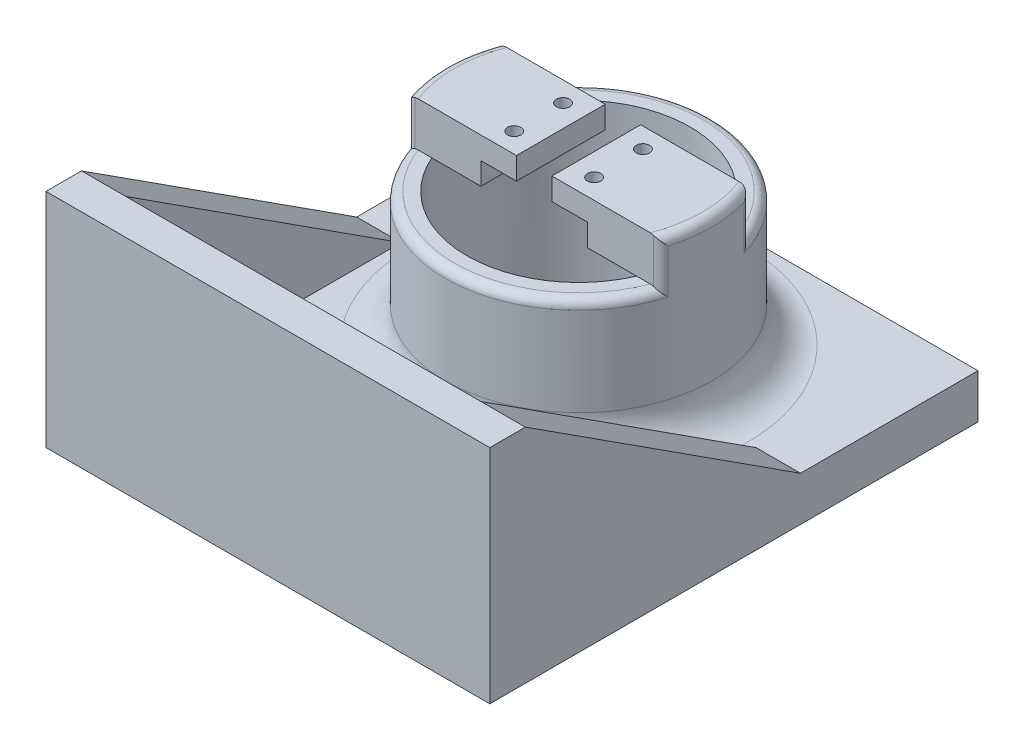
SolidWorks part; units mm, degrees
ref_plane "Front Plane" through (0, 0, 0) normal (0, 0, 1) x (1, 0, 0)
ref_plane "Top Plane" through (0, 0, 0) normal (0, 1, 0) x (1, 0, 0)
ref_plane "Right Plane" through (0, 0, 0) normal (1, 0, 0) x (0, 0, -1)
sketch "Sketch2" plane through (0, 0, 0) normal (0, 1, 0) x (1, 0, 0)
  line L0 (0, 49.9838) -> (0, -58.6525) construction
  line L2 (-50, -70) -> (50, -70)
  line L7 (-50, -70) -> (-50, 40)
  line L8 (-50, 40) -> (50, 40)
  line L9 (50, -70) -> (50, 40)
  line L10 (-50, -70) -> (50, 40) construction
  line L11 (-50, 40) -> (50, -70) construction
  point P3 (0, -15)
  dimension "D1" = 100
  dimension "D2" = 110
  dimension "D3" = 15
extrude "Boss-Extrude1" add sketch "Sketch2" along normal blind 10
sketch "Sketch3" plane through (0, 10, 0) normal (0, 1, 0) x (1, 0, 0)
  line L0 (0, -52.9301) -> (0, 51.772) construction
  circle A1 centre (0, 0) radius 30
  dimension "D1" = 60
extrude "Boss-Extrude2" add sketch "Sketch3" along normal blind 30
sketch "Sketch6" plane through (0, 40, 0) normal (0, 1, 0) x (1, 0, 0)
  circle A0 centre (0, 0) radius 25.15
  dimension "D1" = 50.3
extrude "Cut-Extrude1" cut sketch "Sketch6" against normal through all
sketch "Sketch8" plane through (0, 10, 0) normal (0, 1, 0) x (1, 0, 0)
  line L0 (0, 0) -> (0, -70) construction
  line L1 (-50, -70) -> (50, -70) construction
  line L2 (-23.6557, -50) -> (29.1004, -50) construction
  line L3 (10.3, -31.3978) -> (10.3, -63.6631) construction
  line L9 (-10.7, -60.5) -> (31.3, -60.5)
  line L10 (-10.7, -60.5) -> (-10.7, -39.5)
  line L11 (-10.7, -39.5) -> (31.3, -39.5)
  line L12 (31.3, -60.5) -> (31.3, -39.5)
  line L13 (-10.7, -60.5) -> (31.3, -39.5) construction
  line L14 (-10.7, -39.5) -> (31.3, -60.5) construction
  circle A2 centre (35.2, -45) radius 2.25
  circle A3 centre (35.2, -55) radius 2.25
  circle A4 centre (-14.6, -55) radius 2.25
  circle A5 centre (-14.6, -45) radius 2.25
  point P7 (10.3, -50)
  dimension "D4" = 4.5
  dimension "D1" = 50
  dimension "D2" = 42
  dimension "D3" = 21
  dimension "D5" = 10
  dimension "D6" = 10.3
  dimension "D7" = 49.8
extrude "Cut-Extrude2" cut sketch "Sketch8" against normal through all
sketch "Sketch9" plane through (0, 40, 0) normal (0, 1, 0) x (1, 0, 0)
  line L0 (0, 30) -> (0, -30) construction
  line L1 (-30, 0) -> (30, 0) construction
  line L2 (-28.2843, -10) -> (-4, -10)
  line L3 (-4, -10) -> (-4, 10)
  line L4 (-28.2843, 10) -> (-4, 10)
  line L5 (28.2843, -10) -> (4, -10)
  line L6 (4, -10) -> (4, 10)
  line L7 (28.2843, 10) -> (4, 10)
  circle A0 centre (0, 0) radius 30 construction
  circle A1 centre (0, 0) radius 30 construction
  arc A2 (-28.2843, 10) -> (-28.2843, -10) centre (0, 0) ccw
  circle A3 centre (-9, -5.5) radius 1.5
  circle A4 centre (-9, 5.5) radius 1.5
  circle A5 centre (9, -5.5) radius 1.5
  circle A6 centre (9, 5.5) radius 1.5
  arc A7 (28.2843, -10) -> (28.2843, 10) centre (0, 0) ccw
  point P14 (-4, 0)
  dimension "D5" = 3
  dimension "D1" = 20
  dimension "D2" = 11
  dimension "D3" = 9
  dimension "D4" = 8
extrude "Boss-Extrude3" add sketch "Sketch9" along normal blind 10
sketch "Sketch10" plane through (0, 0, 0) normal (0, 0, 1) x (1, 0, 0)
  line L0 (0, 40) -> (0, 60.9834) construction
  line L1 (28.2843, 40) -> (-28.2843, 40) construction
  line L2 (-12, 40) -> (-12, 45)
  line L3 (-12, 45) -> (12, 45)
  line L5 (12, 40) -> (-12, 40)
  line L6 (12, 40) -> (12, 45)
  point P10 (0, 45)
  dimension "D1" = 24
  dimension "D2" = 5
extrude "Cut-Extrude3" cut sketch "Sketch10" against normal mid plane 20
fillet "Fillet1" radius 8 1 edges at (0, 10, 30)
fillet "Fillet2" radius 2 8 edges at (-30, 50, 0) (28.2843, 45, 10) (30, 50, 0) (28.2843, 45, -10) (0, 40, -30) (-28.2843, 45, -10) (-28.2843, 45, 10) (0, 40, 30)
sketch "Sketch11" plane through (0, 10, 0) normal (0, 1, 0) x (1, 0, 0)
  line L0 (50, -70) -> (50, 40) construction
  line L1 (-50, -70) -> (50, -70)
  line L2 (-50, -70) -> (-50, -62)
  line L3 (-50, -62) -> (50, -62)
  line L4 (50, -70) -> (50, -62)
  dimension "D1" = 8
extrude "Boss-Extrude4" add sketch "Sketch11" along normal blind 40
sketch "Sketch12" plane through (50, 0, 0) normal (1, 0, 0) x (0, 0, -1)
  line L0 (-62, 50) -> (0, 10)
  line L1 (-62, 10) -> (40, 10) construction
  line L2 (0, 10) -> (-62, 10)
  line L3 (-62, 10) -> (-62, 50)
extrude "Boss-Extrude5" add sketch "Sketch12" against normal blind 10
mirror "Mirror1" about plane through (0, 0, 0) normal (1, 0, 0) of "Boss-Extrude5"
